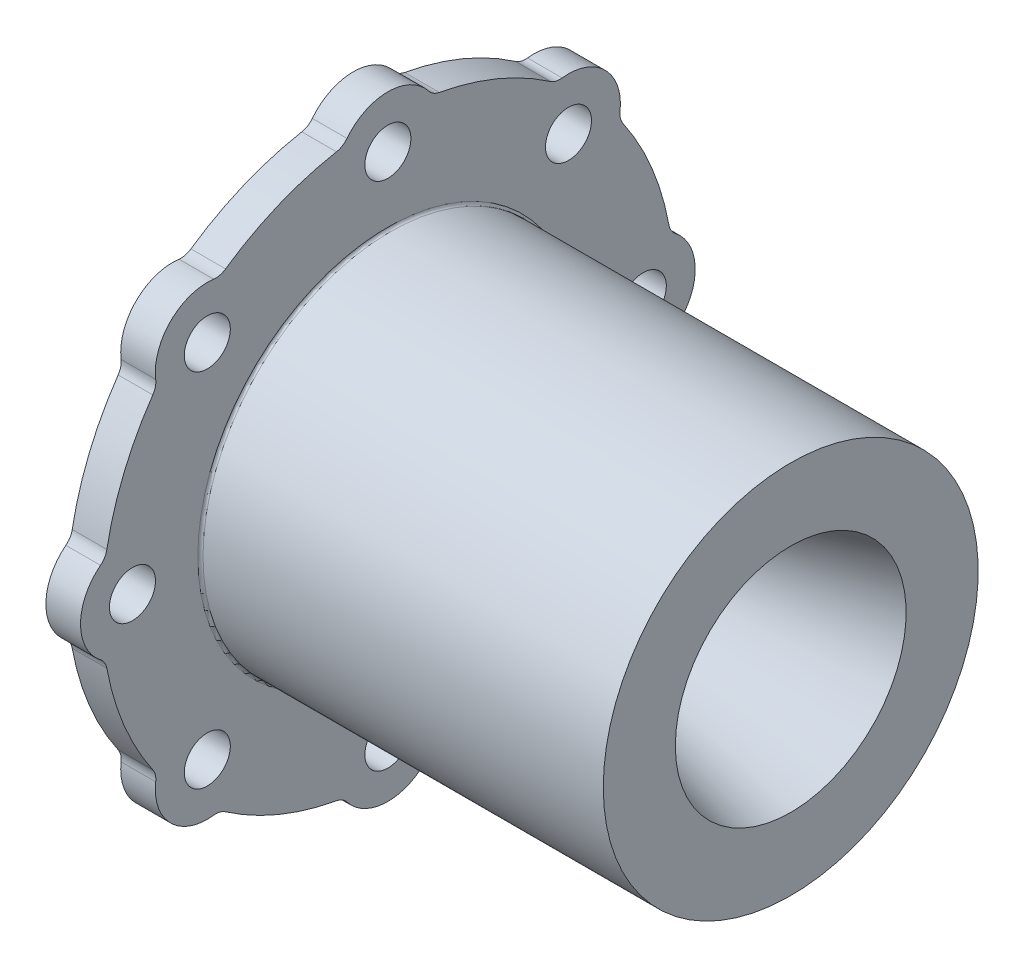
SolidWorks part; units mm, degrees
ref_plane "Front Plane" through (0, 0, 0) normal (0, 0, 1) x (1, 0, 0)
ref_plane "Top Plane" through (0, 0, 0) normal (0, 1, 0) x (1, 0, 0)
ref_plane "Right Plane" through (0, 0, 0) normal (1, 0, 0) x (0, 0, -1)
sketch "Sketch1" plane through (0, 0, 0) normal (0, 0, 1) x (1, 0, 0)
  line L20 (0, 0) -> (32.997, 0) construction
  line L33 (15.4847, 6.946) -> (26.9147, 6.946)
  line L34 (15.4847, 6.946) -> (0, 25.4)
  line L37 (0, 25.4) -> (0, 66.87)
  line L38 (0, 66.87) -> (5.08, 66.87)
  line L39 (5.08, 66.87) -> (5.08, 27.5)
  line L43 (64.1755, 27.5) -> (64.1755, 16.93)
  line L52 (64.1755, 16.93) -> (26.9147, 6.946)
  line L53 (64.1755, 27.5) -> (5.08, 27.5)
  point P1 (2.54, 66.87)
  point P12 (15.4847, 6.946)
  point P24 (26.9147, 6.946)
  dimension "D1" = 6.946
  dimension "D2" = 25.4
  dimension "D5" = 5.08
  dimension "D10" = 15
  dimension "D8" = 16.93
  dimension "D3" = 27.5
  dimension "D4" = 66.87
  dimension "D6" = 11.43
  dimension "D7" = 50
revolve "Nozzle" add sketch "Sketch1" angle 360 about L20
fillet "Rao outlet radius" radius 5.3067 1 edges at (26.9147, 0, 6.946)
sketch "Sketch2" plane through (0, 0, 0) normal (-1, 0, 0) x (0, 0, 1)
  point P0 (37.465, 0)
  point P1 (26.4918, -26.4918)
  point P5 (0, -37.465)
  point P6 (-26.4918, -26.4918)
  point P7 (-37.465, 0)
  point P8 (-26.4918, 26.4918)
  point P9 (0, 37.465)
  point P10 (26.4918, 26.4918)
  point P11 (0, 0)
  dimension "D1" = 37.465
hole_wizard "1/4 Clearance Hole1" positions "Sketch2" profile "Sketch3" hole size "1/4" standard "ANSI Inch" end condition through all
sketch "Sketch3" plane through (0, 0, 37.465) normal (0, 1, 0) x (0, 0, 1)
  line L0 (0, 0) -> (0, 64.1755)
  line L1 (0, 64.1755) -> (3.3782, 64.1755)
  line L2 (3.3782, 64.1755) -> (3.3782, 0)
  line L5 (3.3782, 0) -> (0, 0)
  line L11 (0, -6.35) -> (0, 107.95) construction
  dimension "Thru Hole Dia." = 6.7564
  dimension "Thru Hole Depth" = 64.1755
sketch "Sketch5" plane through (0, 0, 0) normal (1, 0, 0) x (0, 0, -1)
  line L0 (0, 0) -> (0, 85.5504) construction
  arc A32 (6.0027, 42.1589) -> (-6.0027, 42.1589) centre (0, 37.465) ccw
  arc A33 (17.8531, 37.9172) -> (7.5462, 41.225) centre (0, 0) ccw
  arc A51 (-7.5462, 41.225) -> (-14.1874, 39.4356) centre (0, 0) ccw
  arc A69 (6.0027, 42.1589) -> (7.5462, 41.225) centre (8.0035, 43.7235) ccw
  arc A70 (-6.0027, 42.1589) -> (-7.5462, 41.225) centre (-8.0035, 43.7235) cw
  arc A72 (34.0554, 25.5663) -> (25.5663, 34.0554) centre (26.4918, 26.4918) ccw
  arc A73 (39.4356, 14.1874) -> (34.4865, 23.8145) centre (0, 0) ccw
  arc A74 (23.8145, 34.4865) -> (17.8531, 37.9172) centre (0, 0) ccw
  arc A75 (34.0554, 25.5663) -> (34.4865, 23.8145) centre (36.5765, 25.2578) ccw
  arc A76 (25.5663, 34.0554) -> (23.8145, 34.4865) centre (25.2578, 36.5765) cw
  arc A77 (42.1589, -6.0027) -> (42.1589, 6.0027) centre (37.465, 0) ccw
  arc A78 (37.9172, -17.8531) -> (41.225, -7.5462) centre (0, 0) ccw
  arc A79 (41.225, 7.5462) -> (39.4356, 14.1874) centre (0, 0) ccw
  arc A80 (42.1589, -6.0027) -> (41.225, -7.5462) centre (43.7235, -8.0035) ccw
  arc A81 (42.1589, 6.0027) -> (41.225, 7.5462) centre (43.7235, 8.0035) cw
  arc A82 (25.5663, -34.0554) -> (34.0554, -25.5663) centre (26.4918, -26.4918) ccw
  arc A83 (14.1874, -39.4356) -> (23.8145, -34.4865) centre (0, 0) ccw
  arc A84 (34.4865, -23.8145) -> (37.9172, -17.8531) centre (0, 0) ccw
  arc A85 (25.5663, -34.0554) -> (23.8145, -34.4865) centre (25.2578, -36.5765) ccw
  arc A86 (34.0554, -25.5663) -> (34.4865, -23.8145) centre (36.5765, -25.2578) cw
  arc A87 (-6.0027, -42.1589) -> (6.0027, -42.1589) centre (0, -37.465) ccw
  arc A88 (-14.2148, -39.4257) -> (-7.5462, -41.225) centre (0, 0) ccw
  arc A89 (7.5462, -41.225) -> (14.1874, -39.4356) centre (0, 0) ccw
  arc A90 (-6.0027, -42.1589) -> (-7.5462, -41.225) centre (-8.0035, -43.7235) ccw
  arc A91 (6.0027, -42.1589) -> (7.5462, -41.225) centre (8.0035, -43.7235) cw
  arc A92 (-34.0554, -25.5663) -> (-25.5663, -34.0554) centre (-26.4918, -26.4918) ccw
  arc A93 (-37.9194, -17.8486) -> (-34.4865, -23.8145) centre (0, 0) ccw
  arc A94 (-23.8145, -34.4865) -> (-14.2148, -39.4257) centre (0, 0) ccw
  arc A95 (-34.0554, -25.5663) -> (-34.4865, -23.8145) centre (-36.5765, -25.2578) ccw
  arc A96 (-25.5663, -34.0554) -> (-23.8145, -34.4865) centre (-25.2578, -36.5765) cw
  arc A97 (-42.1589, 6.0027) -> (-42.1589, -6.0027) centre (-37.465, 0) ccw
  arc A98 (-39.4483, 14.1519) -> (-41.225, 7.5462) centre (0, 0) ccw
  arc A99 (-41.225, -7.5462) -> (-37.9194, -17.8486) centre (0, 0) ccw
  arc A100 (-42.1589, 6.0027) -> (-41.225, 7.5462) centre (-43.7235, 8.0035) ccw
  arc A101 (-42.1589, -6.0027) -> (-41.225, -7.5462) centre (-43.7235, -8.0035) cw
  arc A102 (-25.5663, 34.0554) -> (-34.0554, 25.5663) centre (-26.4918, 26.4918) ccw
  arc A103 (-14.1874, 39.4356) -> (-23.8145, 34.4865) centre (0, 0) ccw
  arc A104 (-34.4865, 23.8145) -> (-39.4483, 14.1519) centre (0, 0) ccw
  arc A105 (-25.5663, 34.0554) -> (-23.8145, 34.4865) centre (-25.2578, 36.5765) ccw
  arc A106 (-34.0554, 25.5663) -> (-34.4865, 23.8145) centre (-36.5765, 25.2578) cw
  point P1 (0, 48.9722)
  point P69 (0, 0)
  point P78 (-6.5261, 41.3988)
  dimension "D3" = 41.91
  dimension "D4" = 2.54
  dimension "D5" = 37.465
  dimension "D6" = 37.465
  dimension "D1" = 8
extrude "Cut-Extrude1" cut sketch "Sketch5" along normal up to surface (5.08 mm away) flip side to cut up to face at (5.08, 0, 40.8432)
fillet "Fillet1" radius 0.381 1 edges at (5.08, 0, 27.5)
fillet "Rao Inlet radius" radius 20.838 1 edges at (15.4847, 0, 6.946)
equation "\"radius\"= 1in"
equation "\"Flange\" = 0.55in"
equation "\"Length\"= 2cm"
equation "\"Flange_Thickness\"= 0.2in"
equation "\"offset\"= 0.625cm"
equation "\"D2@Sketch1\"=\"radius\""
equation "\"throat\"= 0.6946cm"
equation "\"hole_dia\"= 0.66cm"
equation "\"D1@Sketch1\"=\"throat\""
equation "\"D5@Sketch1\"=\"Flange_Thickness\""
equation "\"Seal_dia\"= 2.5cm"
equation "\"Seal_depth\"= 0.1cm"
equation "\"Seal_width\"= 0.15cm"
equation "\"Nozzle_angle\"= 15"
equation "\"D10@Sketch1\"=\"Nozzle_angle\""
equation "\"nozzle_length\"= 6.34"
equation "\"bolt_head_dia\"=2.3795"
equation "\"bolt_rad\"= \"radius\" + 0.5 * \"Flange\" + 0.2in"
equation "\"scallop_inner_dia\"= 3.3in"
equation "\"exit_rad\"= 1.693cm"
equation "\"D8@Sketch1\"=\"exit_rad\""
equation "\"outside_dia\"= 2.75cm"
equation "\"D3@Sketch1\"=\"outside_dia\""
equation "\"D4@Sketch1\"=\"outside_dia\"+\"Flange\"+\"Buffer\""
equation "\"Scallop_OD\" = 0.6in"
equation "\"D3\"= \"Scallop_OD\" / 2"
equation "\"D4\"= \"scallop_inner_dia\" / 2"
equation "\"D2@Sketch5\"=\"Scallop_OD\"/2"
equation "\"D3@Sketch5\"=\"scallop_inner_dia\"/2"
equation "\"D6@Sketch5\"=\"bolt_rad\""
equation "\"D1@Sketch2\"=\"bolt_rad\""
equation "\"Buffer\"= 1in"
equation "\"D1@Rao Inlet radius\"=3*\"throat\""
equation "\"D1@Rao outlet radius\"=2 * 0.382 * \"throat\""
